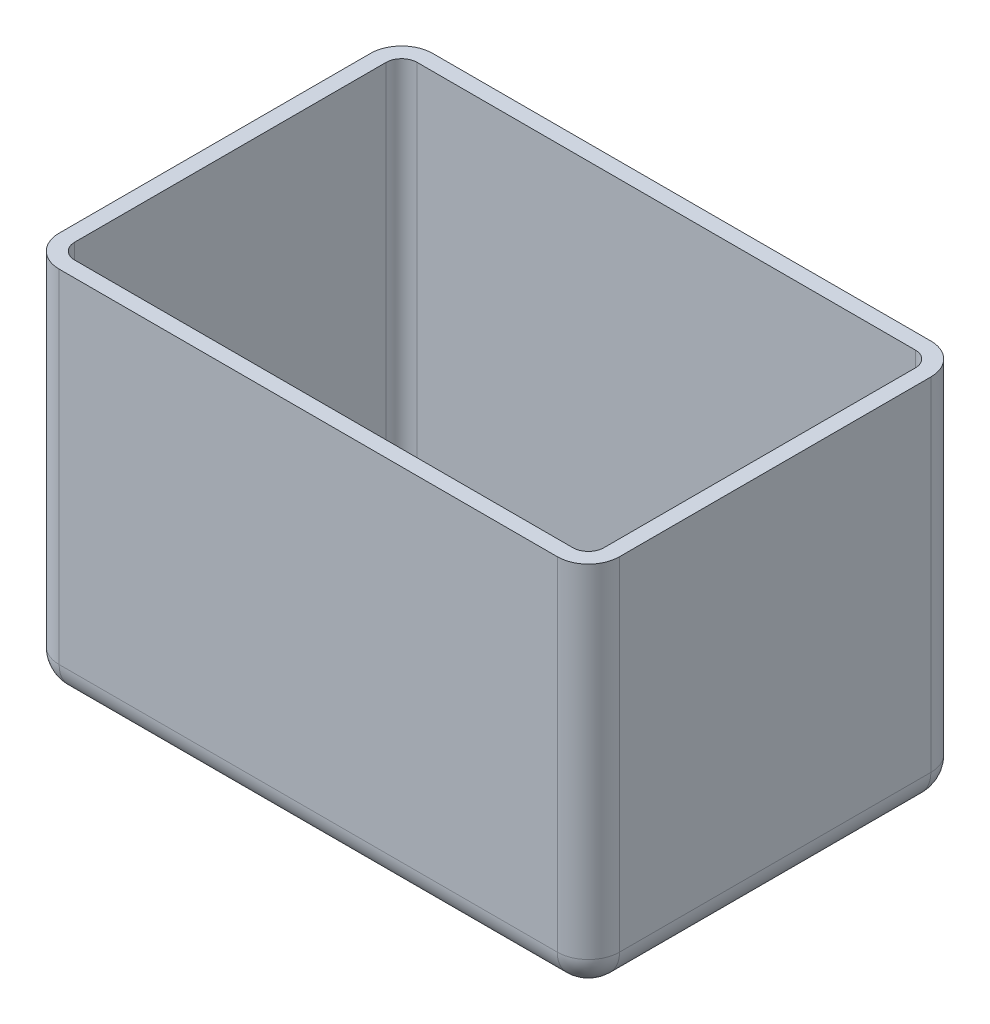
SolidWorks part; units mm, degrees
ref_plane "Front Plane" through (0, 0, 0) normal (0, 0, 1) x (1, 0, 0)
ref_plane "Top Plane" through (0, 0, 0) normal (0, 1, 0) x (1, 0, 0)
ref_plane "Right Plane" through (0, 0, 0) normal (1, 0, 0) x (0, 0, -1)
sketch "Sketch1" plane through (0, 0, 0) normal (0, 1, 0) x (1, 0, 0)
  line L1 (-228.6, -152.4) -> (228.6, -152.4)
  line L2 (-228.6, -152.4) -> (-228.6, 152.4)
  line L3 (-228.6, 152.4) -> (228.6, 152.4)
  line L4 (228.6, -152.4) -> (228.6, 152.4)
  line L5 (-228.6, -152.4) -> (228.6, 152.4) construction
  line L6 (-228.6, 152.4) -> (228.6, -152.4) construction
  point P0 (0, 0)
  dimension "D1" = 304.8
  dimension "D2" = 457.2
extrude "Boss-Extrude1" add sketch "Sketch1" along normal blind 304.8
fillet "Fillet1" radius 25.4 4 edges at (228.6, 0, 0) (0, 0, -152.4) (-228.6, 0, 0) (0, 0, 152.4) type face fillet first side face at (-228.6, 152.4, 0) first side face at (0, 152.4, -152.4) first side face at (0, 152.4, 152.4) first side face at (228.6, 152.4, 0) second side face at (0, 0, 0)
fillet "Fillet2" radius 25.4 1 edges at (228.6, 165.1, 152.4) type face fillet first side face at (0, 165.1, 152.4) second side face at (228.6, 165.1, 0)
fillet "Fillet3" radius 25.4 1 edges at (228.6, 165.1, -152.4) type face fillet first side face at (228.6, 165.1, -12.7) second side face at (0, 165.1, -152.4)
fillet "Fillet4" radius 25.4 1 edges at (-228.6, 165.1, -152.4) type face fillet first side face at (-12.7, 165.1, -152.4) second side face at (-228.6, 165.1, 0)
fillet "Fillet5" radius 25.4 1 edges at (-228.6, 165.1, 152.4) type face fillet first side face at (-228.6, 165.1, 12.7) second side face at (-12.7, 165.1, 152.4)
shell "Shell" thickness 12.7 removed face at (0, 304.8, 0)
ref_plane "Midplane" through (0, 152.4, 0) normal (0, -1, 0) x (-1, 0, 0)
ref_plane "MirrorPlane" through (0, 177.8, 0) normal (0, -1, 0) x (-1, 0, 0)
